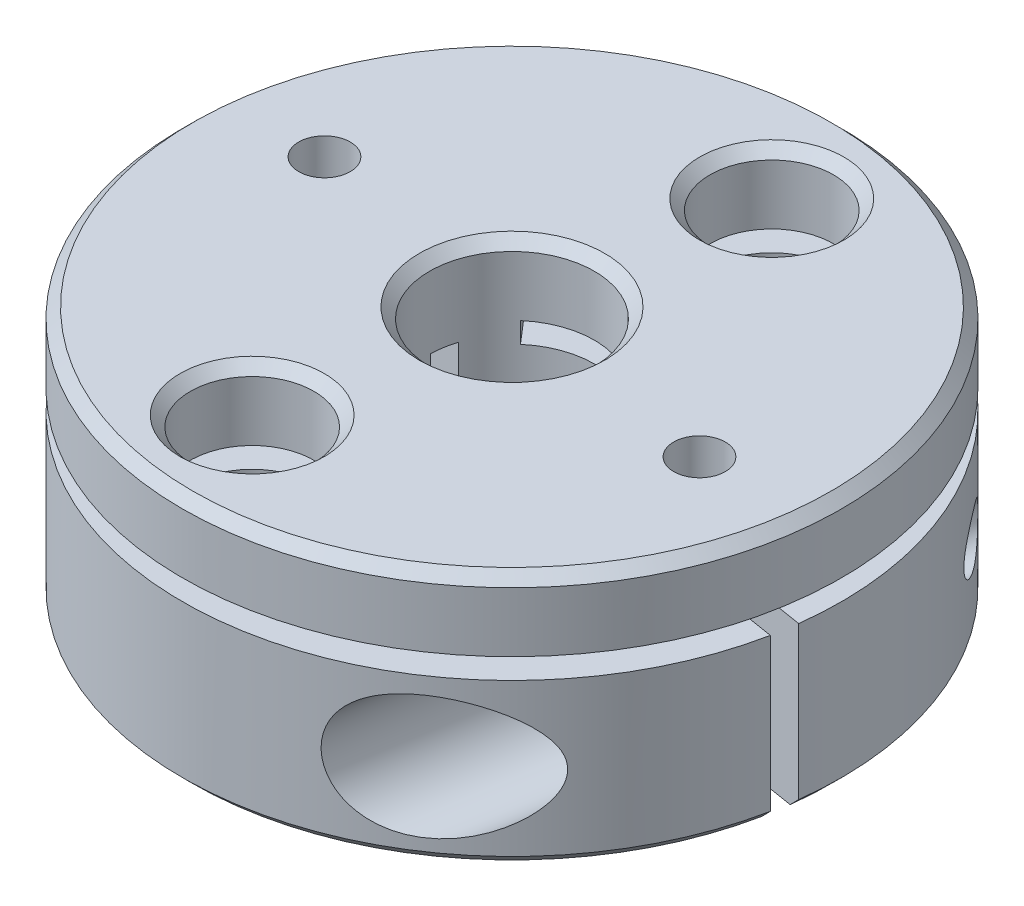
SolidWorks part; units mm, degrees
ref_plane "前视基准面" through (0, 0, 0) normal (0, 0, 1) x (1, 0, 0)
ref_plane "上视基准面" through (0, 0, 0) normal (0, 1, 0) x (1, 0, 0)
ref_plane "右视基准面" through (0, 0, 0) normal (1, 0, 0) x (0, 0, -1)
sketch "草图1" plane through (0, 0, 0) normal (0, 1, 0) x (1, 0, 0)
  circle A0 centre (0, 0) radius 16
  dimension "D1" = 32
extrude "凸台-拉伸1" add sketch "草图1" along normal blind 12.3
sketch "草图2" plane through (0, 12.3, 0) normal (0, 1, 0) x (1, 0, 0)
  line L0 (-2.6148, 3.027) -> (-10.459, 12.1082)
  line L1 (-3.4351, -2.0494) -> (-13.7404, -8.1976)
  circle A0 centre (0, 0) radius 16 construction
  arc A1 (-13.7404, -8.1976) -> (-10.459, 12.1082) centre (0, 0) ccw
  arc A2 (-3.4351, -2.0494) -> (-2.6148, 3.027) centre (0, 0) ccw
  dimension "D1" = 8
  dimension "D2" = 80
extrude "切除-拉伸1" cut sketch "草图2" against normal blind 1 from offset 3.4 offset against normal yes
sketch "草图3" plane through (0, 12.3, 0) normal (0, 1, 0) x (1, 0, 0)
  line L0 (-22.1826, 4.1925) -> (25.6659, -3.5398)
  line L1 (25.6659, -3.5398) -> (25.4745, -4.7244)
  line L2 (25.4745, -4.7244) -> (-22.374, 3.0078)
  line L3 (-22.374, 3.0078) -> (-22.1826, 4.1925)
  line L4 (0, 0) -> (0.0957, 0.5923) construction
  line L5 (-10.459, 12.1082) -> (-2.6148, 3.027) construction
  line L6 (-10.459, 12.1082) -> (-2.6148, 3.027) construction
  point P6 (0, 0)
  point P7 (0, 0)
  dimension "D1" = 1.2
  dimension "D2" = 0.6
  dimension "D3" = 40
extrude "切除-拉伸2" cut sketch "草图3" against normal blind 10 from offset 4 offset against normal yes
sketch "草图4" plane through (-0.0957, 0, 0.5923) normal (0.1595, 0, -0.9872) x (-0.9872, 0, -0.1595)
  line L0 (15.9887, 0) -> (15.9887, 9.0294)
  line L1 (15.9887, 9.0294) -> (5.4593, 9.0294)
  line L2 (5.4593, 9.0294) -> (14.4887, 0)
  line L3 (-15.9887, 0) -> (15.9887, 0) construction
  line L4 (14.4887, 0) -> (15.9887, 0)
  dimension "D1" = 1.5
  dimension "D2" = 45
extrude "凸台-拉伸2" add sketch "草图4" along normal blind 1.2
sketch "草图5" plane through (0, 12.3, 0) normal (0, 1, 0) x (1, 0, 0)
  line L0 (-15.6883, 3.143) -> (-15.8797, 1.9584) construction
  line L1 (-15.6883, 3.143) -> (-15.8797, 1.9584)
  arc A0 (-15.6883, 3.143) -> (-15.8797, 1.9584) centre (0, 0) ccw
extrude "凸台-拉伸3" add sketch "草图5" against normal up to surface (12.3 mm away) up to face at (-4.7677, 0, -0.7705)
sketch "草图6" plane through (0, 12.3, 0) normal (0, 1, 0) x (1, 0, 0)
  circle A0 centre (0, 0) radius 4
  dimension "D1" = 8
extrude "切除-拉伸3" cut sketch "草图6" against normal blind 22.2
sketch "草图7" plane through (0, 0, 0) normal (0, -1, 0) x (1, 0, 0)
  line L0 (0, 0) -> (-1.7548, 10.8591) construction
  line L1 (3.8084, 1.2232) -> (15.6883, 3.143) construction
  circle A0 centre (-1.7548, 10.8591) radius 3
  circle A1 centre (1.7548, -10.8591) radius 3
  point P11 (0, 0)
  dimension "D2" = 6
  dimension "D1" = 11
  dimension "D3" = 2
extrude "切除-拉伸4" cut sketch "草图7" against normal blind 22.2
sketch "草图8" plane through (0, 0, 0) normal (0, -1, 0) x (1, 0, 0)
  line L0 (-10.8591, -1.7548) -> (0, 0) construction
  line L1 (-14.3989, -1.7191) -> (-3.9998, -0.0386) construction
  circle A0 centre (-10.8591, -1.7548) radius 1.25
  circle A1 centre (10.8591, 1.7548) radius 1.25
  point P11 (0, 0)
  dimension "D1" = 2.5
  dimension "D2" = 11
  dimension "D3" = 2
extrude "切除-拉伸5" cut sketch "草图8" against normal blind 22.2
sketch "草图9" plane through (-0.0957, 0, 0.5923) normal (0.1595, 0, -0.9872) x (-0.9872, 0, -0.1595)
  line L0 (-12.0966, 5.7459) -> (-9.9034, 5.7459) construction
  line L2 (-12.0966, 0) -> (-12.0966, 7.9) construction
  line L3 (-9.9034, 7.9) -> (-9.9034, 0) construction
  circle A0 centre (-11, 4.0843) radius 1.25
  point P8 (0, 0)
  point P9 (-11, 5.7459)
  dimension "D1" = 2.5
extrude "切除-拉伸6" cut sketch "草图9" against normal blind 22.2 and the other way blind 22.2
sketch "草图10" plane through (-0.0957, 0, 0.5923) normal (0.1595, 0, -0.9872) x (-0.9872, 0, -0.1595)
  circle A0 centre (-11, 4.0843) radius 3
  dimension "D1" = 6
extrude "切除-拉伸7" cut sketch "草图10" against normal blind 22.2 from offset 4 offset against normal yes
chamfer "倒角1" distance 0.5 angle 45 9 edges at (-15.7951, 0, -2.5525) (0, 12.3, 16) (1.7548, 0, -13.8591) (0.6381, 0, -3.9488) (-0.6381, 0, 3.9488) (-1.7548, 0, 7.8591) (-1.7548, 12.3, 13.8591) (1.7548, 12.3, -7.8591) (0, 12.3, 4)
